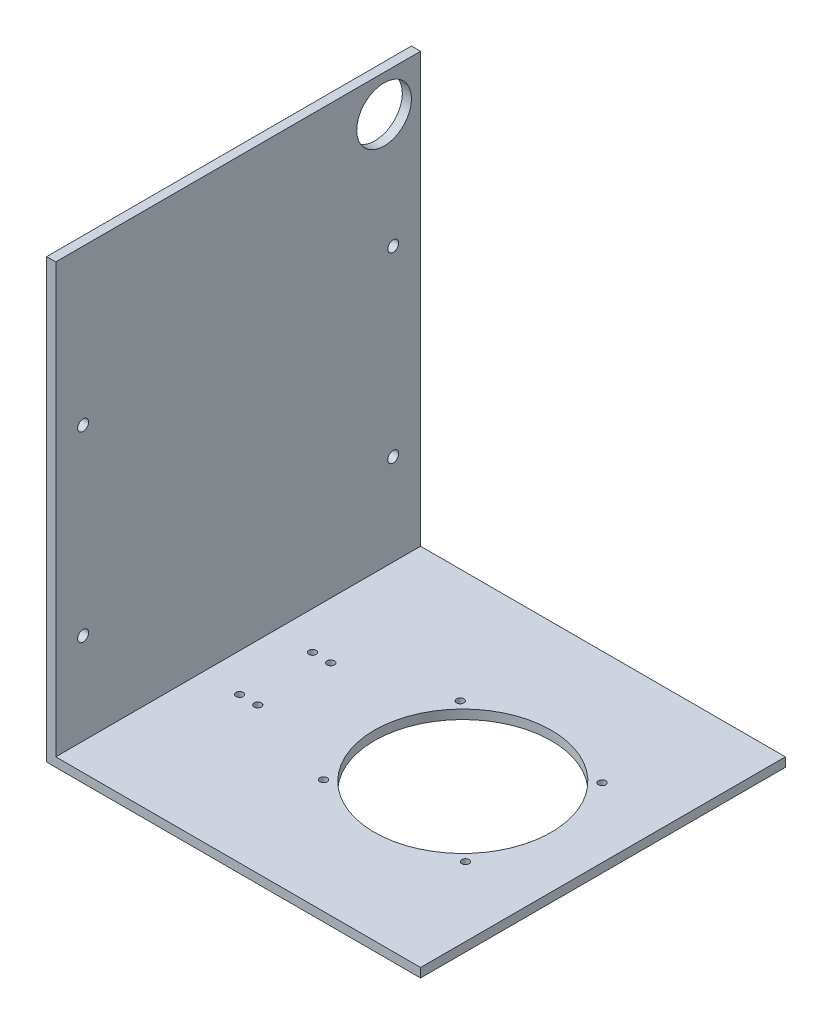
SolidWorks part; units mm, degrees
ref_plane "Front Plane" through (0, 0, 0) normal (0, 0, 1) x (1, 0, 0)
ref_plane "Top Plane" through (0, 0, 0) normal (0, 1, 0) x (1, 0, 0)
ref_plane "Right Plane" through (0, 0, 0) normal (1, 0, 0) x (0, 0, -1)
sketch "Sketch1" plane through (0, 0, 0) normal (0, 0, 1) x (1, 0, 0)
  line L0 (0, 240) -> (0, 0)
  line L1 (0, 0) -> (205, 0)
  line L2 (205, 0) -> (205, 5)
  line L3 (205, 5) -> (5, 5)
  line L4 (5, 5) -> (5, 240)
  line L5 (5, 240) -> (0, 240)
  dimension "D1" = 5
  dimension "D2" = 5
  dimension "D3" = 200
  dimension "D4" = 235
extrude "Boss-Extrude1" add sketch "Sketch1" along normal blind 200
sketch "Sketch2" plane through (0, 5, 0) normal (0, 1, 0) x (1, 0, 0)
  line L0 (205, -100) -> (0, -100) construction
  line L1 (205, -200) -> (205, 0) construction
  line L2 (0, -200) -> (0, 0) construction
  line L4 (167.0574, -137.4644) -> (89.2778, -137.4644) construction
  line L5 (167.0574, -137.4644) -> (167.0574, -62.5356) construction
  line L6 (167.0574, -62.5356) -> (89.2778, -62.5356) construction
  line L7 (89.2778, -137.4644) -> (89.2778, -62.5356) construction
  line L8 (167.0574, -137.4644) -> (89.2778, -62.5356) construction
  line L9 (167.0574, -62.5356) -> (89.2778, -137.4644) construction
  circle A0 centre (128.1676, -100) radius 48.5
  circle A1 centre (89.2778, -62.5356) radius 2
  circle A2 centre (167.0574, -62.5356) radius 2
  circle A3 centre (89.2778, -137.4644) radius 2
  circle A4 centre (167.0574, -137.4644) radius 2
  dimension "D1" = 97
  dimension "D2" = 4
  dimension "D3" = 108
extrude "Cut-Extrude1" cut sketch "Sketch2" against normal up to next
sketch "Sketch3" plane through (0, 5, 0) normal (0, 1, 0) x (1, 0, 0)
  line L0 (30.75, 0) -> (30.75, -200) construction
  line L1 (205, 0) -> (5, 0) construction
  line L2 (205, -200) -> (5, -200) construction
  line L3 (30.75, -200) -> (30.75, -71.2391) construction
  line L4 (-16.5042, -100) -> (30.75, -100) construction
  line L6 (5, -200) -> (5, 0) construction
  circle A0 centre (25.75, -80) radius 2
  circle A1 centre (25.75, -120) radius 2
  circle A2 centre (35.75, -120) radius 2
  circle A3 centre (35.75, -80) radius 2
  point P10 (7.1229, -100)
  dimension "D2" = 40
  dimension "D3" = 10
  dimension "D4" = 4
  dimension "D1" = 25.75
extrude "Cut-Extrude2" cut sketch "Sketch3" against normal up to next
sketch "Sketch4" plane through (5, 0, 0) normal (1, 0, 0) x (0, 0, -1)
  line L0 (0, 5) -> (0, 240) construction
  line L1 (-200, 240) -> (0, 240) construction
  circle A0 centre (-20, 220) radius 15
  dimension "D1" = 30
  dimension "D2" = 20
  dimension "D3" = 20
extrude "Cut-Extrude3" cut sketch "Sketch4" against normal blind 10
sketch "Sketch5" plane through (5, 0, 0) normal (1, 0, 0) x (0, 0, -1)
  line L0 (-100, 240) -> (-100, 5) construction
  line L1 (-200, 240) -> (0, 240) construction
  line L2 (-200, 5) -> (0, 5) construction
  line L3 (-185, 240) -> (-185, 5) construction
  line L4 (-200, 5) -> (-200, 240) construction
  circle A0 centre (-185, 55) radius 3
  circle A1 centre (-185, 155) radius 3
  circle A2 centre (-15, 55) radius 3
  circle A3 centre (-15, 155) radius 3
  dimension "D2" = 100
  dimension "D3" = 6
  dimension "D1" = 50
  dimension "D4" = 15
extrude "Cut-Extrude4" cut sketch "Sketch5" against normal up to next
